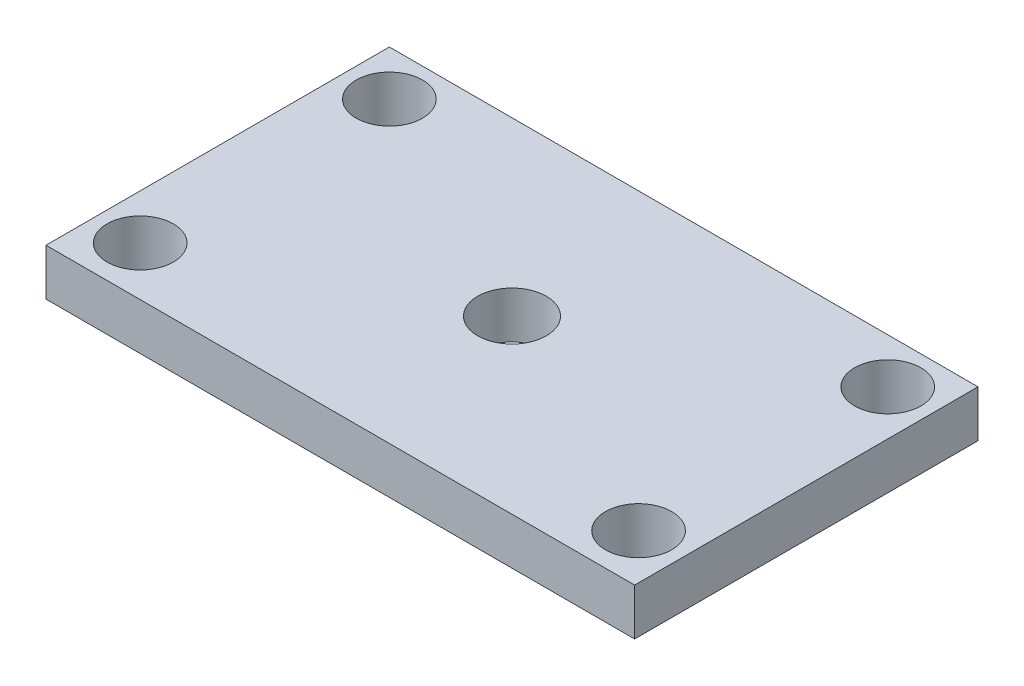
SolidWorks part; units mm, degrees
ref_plane "Front Plane" through (0, 0, 0) normal (0, 0, 1) x (1, 0, 0)
ref_plane "Top Plane" through (0, 0, 0) normal (0, 1, 0) x (1, 0, 0)
ref_plane "Right Plane" through (0, 0, 0) normal (1, 0, 0) x (0, 0, -1)
sketch "Sketch1" plane through (0, 0, 0) normal (0, 1, 0) x (1, 0, 0)
  line L0 (4.6, 30.4) -> (0, 30.4) construction
  line L1 (0, 0) -> (60, 0)
  line L2 (0, 0) -> (0, 35)
  line L3 (0, 35) -> (60, 35)
  line L4 (60, 0) -> (60, 35)
  line L5 (4.6, 30.4) -> (55.4, 30.4) construction
  line L6 (4.6, 30.4) -> (4.6, 5) construction
  line L7 (4.6, 5) -> (55.4, 5) construction
  line L8 (55.4, 30.4) -> (55.4, 5) construction
  line L9 (4.6, 30.4) -> (4.6, 35) construction
  circle A0 centre (4.6, 30.4) radius 3.3782
  circle A1 centre (55.4, 30.4) radius 3.3782
  circle A2 centre (4.6, 5) radius 3.3782
  circle A3 centre (55.4, 5) radius 3.3782
  circle A4 centre (30, 17.5) radius 3.5
  point P13 (30, 30.4)
  point P14 (30, 35)
  point P20 (60, 17.5)
  dimension "D5" = 6.7564
  dimension "D6" = 7
  dimension "D1" = 60
  dimension "D2" = 35
  dimension "D3" = 50.8
  dimension "D4" = 25.4
extrude "Boss-Extrude1" add sketch "Sketch1" along normal blind 4.7625
